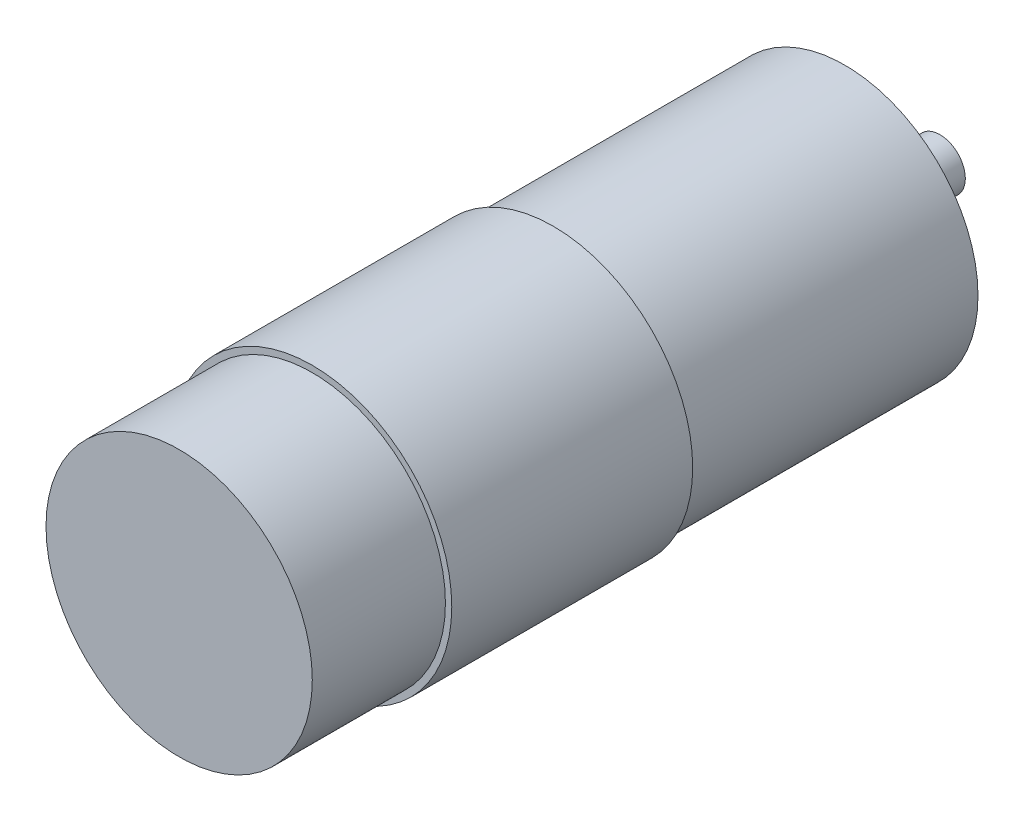
SolidWorks part; units mm, degrees
ref_plane "정면" through (0, 0, 0) normal (0, 0, 1) x (1, 0, 0)
ref_plane "윗면" through (0, 0, 0) normal (0, 1, 0) x (1, 0, 0)
ref_plane "우측면" through (0, 0, 0) normal (1, 0, 0) x (0, 0, -1)
sketch "스케치1" plane through (0, 0, 0) normal (0, 0, 1) x (1, 0, 0)
  circle A0 centre (0, 0) radius 21
  circle A1 centre (0, 0) radius 4
  circle A2 centre (0, 0) radius 12.5
  dimension "D1" = 42
  dimension "D2" = 8
  dimension "D3" = 25
extrude "보스-돌출1" add sketch "스케치1" along normal blind 105 contours A0 A1 | A1 | A2 A1 | A1 | A0 region at (-20.406, 0, 0) region at (0, 0, 0) region at (-12.1464, 0, 0)
sketch "스케치3" plane through (0, 0, 0) normal (0, 0, -1) x (-1, 0, 0)
  circle A0 centre (0, 0) radius 22
  dimension "D1" = 44
extrude "보스-돌출3" add sketch "스케치3" against normal blind 38 from offset 46 offset against normal yes
extrude "보스-돌출4" add sketch "스케치1<4>" against normal blind 2 contours A2 A1 | A1 region at (0, 0, 0) region at (-12.1464, 0, 0)
sketch "스케치1<4>" plane through (0, 0, 0) normal (0, 0, 1) x (1, 0, 0) same geometry as "스케치1"
extrude "보스-돌출5" add sketch "스케치1<5>" against normal blind 13 from surface contours A1 region at (0, 0, 0) starting at face at (12.5, 0, -2)
sketch "스케치1<5>" plane through (0, 0, 0) normal (0, 0, 1) x (1, 0, 0) same geometry as "스케치1"
sketch "스케치4" plane through (0, 0, 0) normal (0, 0, -1) x (-1, 0, 0)
  circle A0 centre (0, 0) radius 17.5 construction
  circle A1 centre (0, 0) radius 21
  circle A2 centre (0, 0) radius 21
  circle A3 centre (0, -17.5) radius 1.5
  dimension "D3" = 3
  dimension "D1" = 0
  dimension "D2" = 3.5
extrude "컷-돌출1" cut sketch "스케치4" against normal blind 6.5 contours A3 region at (0, -17.5, 0)
pattern_circular "원형 패턴1" count 4 over 360 about axis through (0, 0, 105) along (0, 0, -1) of "컷-돌출1" reverse direction yes
